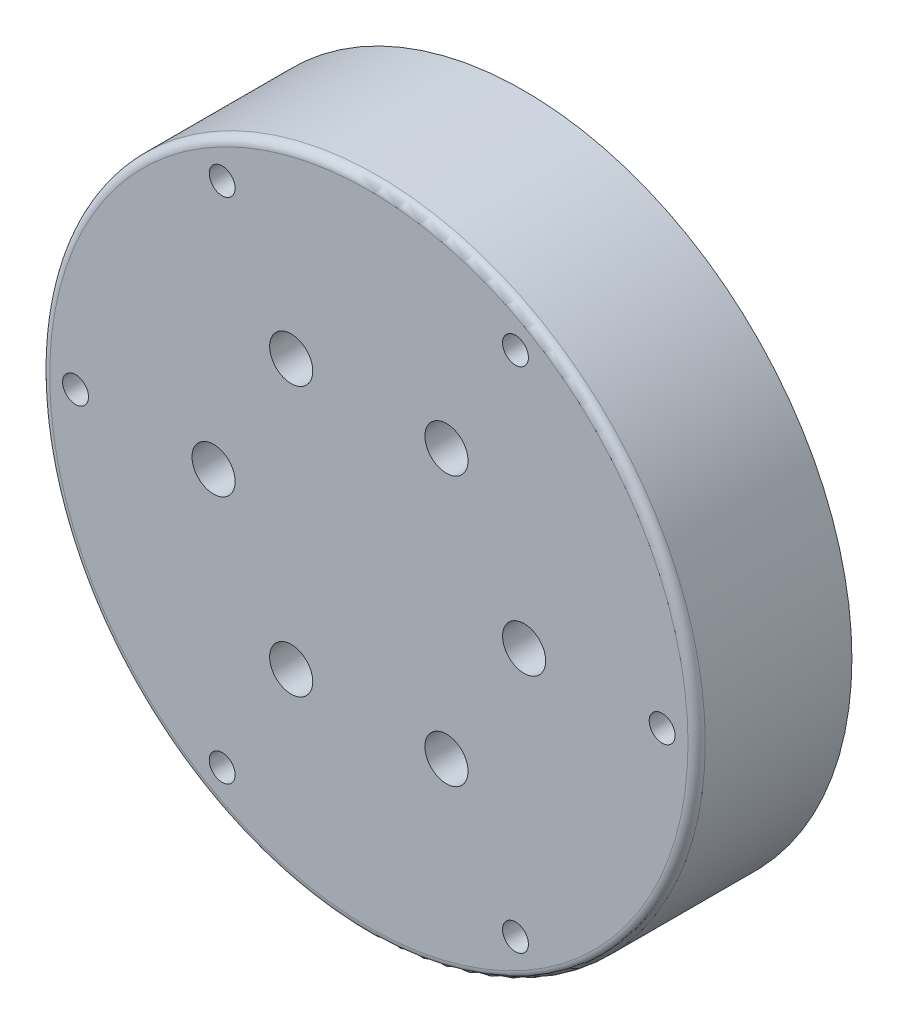
SolidWorks part; units mm, degrees
material "ABS"
ref_plane "Спереди" through (0, 0, 0) normal (0, 0, 1) x (1, 0, 0)
ref_plane "Сверху" through (0, 0, 0) normal (0, 1, 0) x (1, 0, 0)
ref_plane "Справа" through (0, 0, 0) normal (1, 0, 0) x (0, 0, -1)
other "Configuration Table"
sketch "Эскиз1" plane through (0, 0, 0) normal (0, 0, 1) x (1, 0, 0)
  circle A0 centre (0, 0) radius 38
  dimension "D1" = 76
extrude "Бобышка-Вытянуть1" add sketch "Эскиз1" along normal blind 18
sketch "Эскиз2" plane through (0, 0, 18) normal (0, 0, 1) x (1, 0, 0)
  line L0 (0, 0) -> (-34, 0) construction
  line L1 (0, 0) -> (-17, 29.4449) construction
  circle A0 centre (0, 0) radius 34 construction
  circle A1 centre (-34, 0) radius 1.5
  circle A2 centre (0, 0) radius 34 construction
  circle A3 centre (-17, 29.4449) radius 1.5
  circle A4 centre (0, 0) radius 34 construction
  circle A5 centre (17, 29.4449) radius 1.5
  circle A6 centre (0, 0) radius 34 construction
  circle A7 centre (34, 0) radius 1.5
  circle A8 centre (0, 0) radius 34 construction
  circle A9 centre (17, -29.4449) radius 1.5
  circle A10 centre (0, 0) radius 34 construction
  circle A11 centre (-17, -29.4449) radius 1.5
  dimension "D1" = 68
  dimension "D2" = 3
  dimension "D4" = 60
  dimension "D3" = 6
extrude "Вырез-Вытянуть1" cut sketch "Эскиз2" against normal up to next contours A7 | A5 | A3 | A1 | A11 | A9
sketch "Эскиз3" plane through (0, 0, 0) normal (0, 0, -1) x (-1, 0, 0)
  line L0 (-13.0767, -27) -> (13.0767, -27)
  arc A0 (13.0767, -27) -> (-13.0767, -27) centre (0, 0) ccw
  dimension "D1" = 60
  dimension "D2" = 27
extrude "Вырез-Вытянуть2" cut sketch "Эскиз3" against normal blind 12.5
fillet "Скругление1" radius 1 1 edges at (38, 0, 18)
ref_plane "Плоскость1" through (0, -27, 0) normal (0, 1, 0) x (1, 0, 0)
sketch "Эскиз6" plane through (0, -27, 0) normal (0, 1, 0) x (1, 0, 0)
  line L0 (38, 0) -> (-38, 0) construction
  line L1 (-10, -8.5) -> (10, -8.5)
  line L2 (-10, -8.5) -> (-10, -12.5)
  line L3 (-10, -12.5) -> (10, -12.5)
  line L4 (10, -8.5) -> (10, -12.5)
  line L5 (-10, -8.5) -> (10, -12.5) construction
  line L6 (-10, -12.5) -> (10, -8.5) construction
  line L7 (0, 24) -> (0, -24) construction
  point P0 (0, -10.5)
  point P11 (0, 0)
  dimension "D1" = 4
  dimension "D2" = 20
  dimension "D3" = 8.5
  dimension "D4" = 10
extrude "Вырез-Вытянуть7" cut sketch "Эскиз6" against normal up to next
sketch "Эскиз7" plane through (0, 0, 18) normal (0, 0, 1) x (1, 0, 0)
  line L0 (0, 0) -> (-18, 0) construction
  circle A1 centre (0, 0) radius 18 construction
  circle A2 centre (-18, 0) radius 2.5
  circle A4 centre (-9, 15.5885) radius 2.5
  circle A6 centre (9, 15.5885) radius 2.5
  circle A8 centre (18, 0) radius 2.5
  circle A10 centre (9, -15.5885) radius 2.5
  circle A12 centre (-9, -15.5885) radius 2.5
  circle A13 centre (0, 0) radius 18 [skipped]
  circle A14 centre (0, 0) radius 18 [skipped]
  circle A15 centre (0, 0) radius 18 [skipped]
  circle A16 centre (0, 0) radius 18 [skipped]
  circle A17 centre (0, 0) radius 18 [skipped]
  dimension "D3" = 6
  dimension "D1" = 36
  dimension "D2" = 5
extrude "Вырез-Вытянуть8" cut sketch "Эскиз7" against normal up to next
